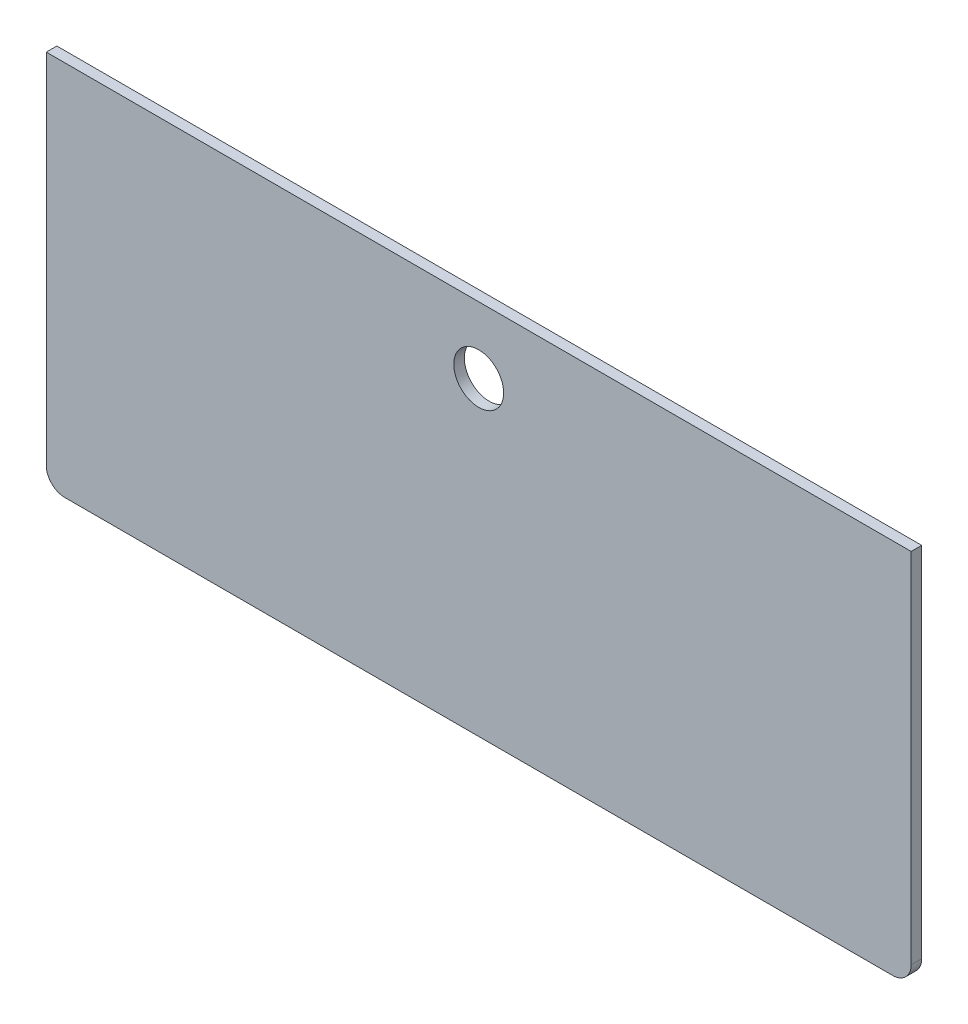
SolidWorks part; units mm, degrees
material "5052-H32"
ref_plane "Front Plane" through (0, 0, 0) normal (0, 0, 1) x (1, 0, 0)
ref_plane "Top Plane" through (0, 0, 0) normal (0, 1, 0) x (1, 0, 0)
ref_plane "Right Plane" through (0, 0, 0) normal (1, 0, 0) x (0, 0, -1)
sketch "Sketch1" plane through (0, 0, 0) normal (0, 0, 1) x (1, 0, 0)
  line L0 (-156.7654, 27.1868) -> (-156.7654, -85.9882)
  line L1 (-156.7654, -85.9882) -> (103.2346, -85.9882)
  line L2 (103.2346, -85.9882) -> (103.2346, 27.1868)
  line L3 (103.2346, 27.1868) -> (-156.7654, 27.1868)
  line L4 (-26.7654, 27.1868) -> (-26.7654, 7.1868) construction
  circle A0 centre (-26.7654, 7.1868) radius 7.5
  dimension "D4" = 15
  dimension "D1" = 113.175
  dimension "D2" = 260
  dimension "D3" = 20
extrude "Boss-Extrude1" add sketch "Sketch1" along normal blind 3.175
fillet "Fillet1" radius 5.5562 2 edges at (-156.7654, -85.9882, 1.5875) (103.2346, -85.9882, 1.5875)
equation "\"L\"= 500"
equation "\"W\"= 260"
equation "\"H\"= 110"
equation "\"Compartment Width\"= 90"
equation "\"T\"= 4.7625 * 2 / 3"
equation "\"Inside Fillet Radius\"= 5.55625"
equation "\"D1@Boss-Extrude1\"=\"T\""
equation "\"D1@Fillet1\"=\"Inside Fillet Radius\""
equation "\"Hole\"=15"
equation "\"D4@Sketch1\"=\"Hole\""
equation "\"D2@Sketch1\"=\"W\""
equation "\"D1@Sketch1\"=\"H\"+\"T\""
